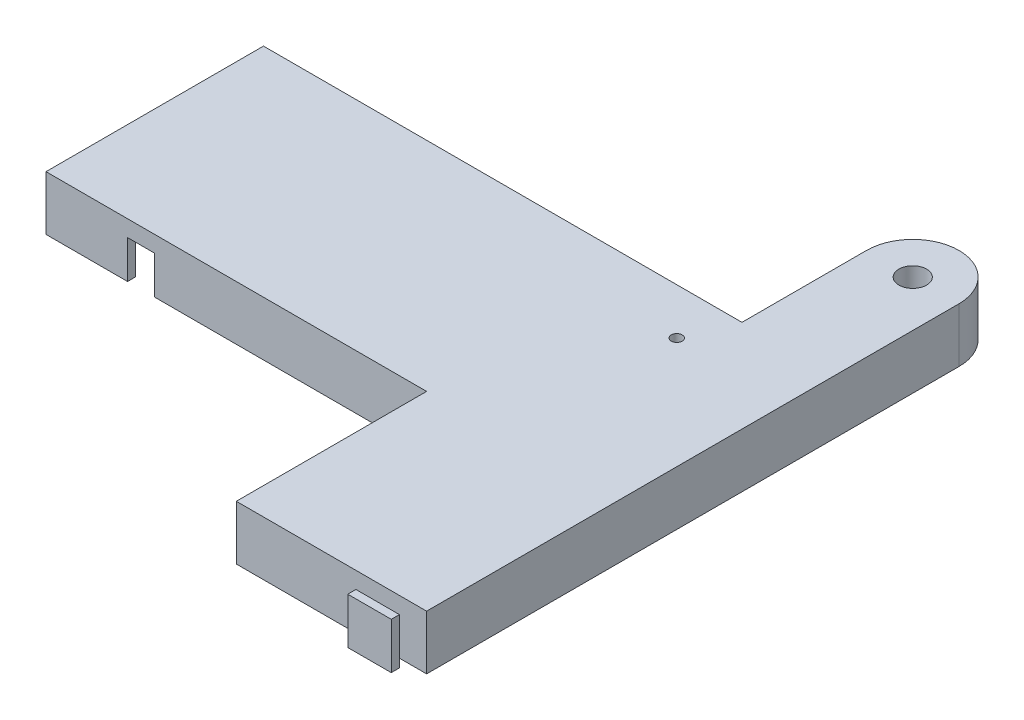
SolidWorks part; units mm, degrees
ref_plane "Front Plane" through (0, 0, 0) normal (0, 0, 1) x (1, 0, 0)
ref_plane "Top Plane" through (0, 0, 0) normal (0, 1, 0) x (1, 0, 0)
ref_plane "Right Plane" through (0, 0, 0) normal (1, 0, 0) x (0, 0, -1)
sketch "CornerSketch1" plane through (0, 0, 0) normal (0, 1, 0) x (1, 0, 0)
  line L0 (210, -70) -> (140, -70)
  line L2 (0, 80) -> (176, 80)
  line L5 (140, -70) -> (140, 0)
  line L6 (140, 0) -> (0, 0)
  line L7 (0, 80) -> (0, 0)
  line L8 (176, 125.825) -> (176, 80)
  line L10 (210, 125.825) -> (210, -70)
  arc A0 (210, 125.825) -> (176, 125.825) centre (193, 125.825) ccw
  dimension "D3" = 34
  dimension "D4" = 70
  dimension "D6" = 45.825
  dimension "D2" = 210
  dimension "D5" = 150
  dimension "D7" = 80
extrude "CornerBoss-Extrude1" add sketch "CornerSketch1" along normal blind 20
shell "Shell1" thickness 3 removed face at (131.5, 0, -36.0813)
sketch "PadSketch2" plane through (0, 17, 0) normal (0, -1, 0) x (1, 0, 0)
  line L0 (210, 70) -> (210, -125.825) construction
  line L1 (176, -80) -> (0, -80) construction
  circle A0 centre (193, -125.825) radius 12
  circle A1 centre (169, -63) radius 5
  dimension "D2" = 10
  dimension "D1" = 24
  dimension "D3" = 41
  dimension "D4" = 17
extrude "PadBoss-Extrude2" add sketch "PadSketch2" along normal blind 10
sketch "StepperRodHoleSketch3" plane through (0, 7, 0) normal (0, -1, 0) x (1, 0, 0)
  circle A0 centre (193, -125.825) radius 5.1
  circle A1 centre (169, -63) radius 2
  dimension "D1" = 10.2
  dimension "D2" = 4
extrude "StepperRodHoleCut-Extrude1" cut sketch "StepperRodHoleSketch3" against normal through all
sketch "ThreadedNutMountHolesSketch4" plane through (0, 7, 0) normal (0, -1, 0) x (-1, 0, 0)
  circle A8 centre (-193, 133.825) radius 1
  circle A9 centre (-185, 125.825) radius 1
  circle A10 centre (-201, 125.825) radius 1
  circle A11 centre (-193, 117.825) radius 1
  dimension "D1" = 2
  dimension "D3" = 16
  dimension "D4" = 8
  dimension "D5" = 16
extrude "ThreadedNutMountHolesCut-Extrude2" cut sketch "ThreadedNutMountHolesSketch4" against normal blind 10
sketch "TLPegHoleSketch1" plane through (0, 0, 0) normal (-1, 0, 0) x (0, 0, 1)
  line L1 (-70, 14) -> (-60, 14)
  line L2 (-70, 14) -> (-70, 0)
  line L3 (-70, 0) -> (-60, 0)
  line L4 (-60, 14) -> (-60, 0)
  line L7 (-80, 0) -> (0, 0) construction
  line L8 (-80, 20) -> (-80, 0) construction
  dimension "D2" = 10
  dimension "D1" = 10
  dimension "D3" = 14
extrude "TLPegHoleCut-Extrude1" cut sketch "TLPegHoleSketch1" against normal blind 3
sketch "BottomPegSketch2" plane through (0, 0, 70) normal (0, 0, 1) x (1, 0, 0)
  line L1 (190.1, 13.9) -> (199.9, 13.9)
  line L2 (190.1, 13.9) -> (190.1, 0)
  line L3 (190.1, 0) -> (199.9, 0)
  line L4 (199.9, 13.9) -> (199.9, 0)
  line L6 (210, 20) -> (210, 0) construction
  line L7 (140, 0) -> (210, 0) construction
  dimension "D2" = 13.9
  dimension "D3" = 9.8
  dimension "D1" = 10.1
extrude "BottomPegBoss-Extrude1" add sketch "BottomPegSketch2" along normal blind 3.1
sketch "BottomPegCapSketch3" plane through (0, 0, 73.1) normal (0, 0, 1) x (1, 0, 0)
  line L1 (187.1, 17) -> (203.1, 17)
  line L2 (187.1, 17) -> (187.1, 0)
  line L3 (187.1, 0) -> (203.1, 0)
  line L4 (203.1, 17) -> (203.1, 0)
  line L6 (140, 0) -> (190.1, 0) construction
  line L7 (190.1, 13.9) -> (190.1, 0) construction
  dimension "D1" = 16
  dimension "D3" = 17
  dimension "D2" = 3
extrude "BottomPegCapBoss-Extrude2" add sketch "BottomPegCapSketch3" along normal blind 3
sketch "BedCenterHoleCutSketch1" plane through (0, 0, 0) normal (0, 0, 1) x (1, 0, 0)
  line L0 (0, 0) -> (140, 0) construction
  line L1 (30, 14) -> (40, 14)
  line L2 (30, 14) -> (30, 0)
  line L3 (30, 0) -> (40, 0)
  line L4 (40, 14) -> (40, 0)
  line L5 (140, 20) -> (140, 0) construction
  dimension "D2" = 10
  dimension "D1" = 14
  dimension "D3" = 100
extrude "BedCenterHoleCut-Extrude1" cut sketch "BedCenterHoleCutSketch1" against normal blind 3
equation "\"BedThickness\"= 20mm"
equation "\"BedToBuildPlateStandoffHolesDistanceFromLeftOrRight\"= \"BuildPlateStandoffHolesDistanceFromLeftOrRight\" + \"BedIncreasedByWidth\" / 2'Equals 17"
equation "\"BedToBuildPlateStandoffHolesDistanceFromBack\"= \"BuildPlateStandoffHolesDistanceFromBack\" + \"BedIncreasedByLength\" / 2'Equals 41"
equation "\"BedLLongSide\"= \"BedThirdSize\" * 3'Equals 210"
equation "\"BedLShortSide\"= \"BedThirdSize\" * 2'Equals 140"
equation "\"BedIncreasedByWidth\"= 20mm"
equation "\"BedIncreasedByLength\"= 0mm"
equation "\"BedThirdSize\"= 70mm"
equation "\"BedOverlap\"= 20mm"
equation "\"D3@TLPegHoleSketch1\"=\"BedPegHoleHeight\""
equation "\"StandardWallThickness\"= 3mm"
equation "\"D1@CornerBoss-Extrude1\"=\"BedThickness\""
equation "\"D1@TLPegHoleCut-Extrude1\" = \"StandardWallThickness\""
equation "\"D1@BottomPegBoss-Extrude1\"=\"BedPegBoss\""
equation "\"D2@BottomPegCapSketch3\"=\"StandardWallThickness\""
equation "\"D1@BottomPegCapBoss-Extrude2\" = \"StandardWallThickness\""
equation "\"LeadScrewNutPadSize\"= \"LeadScrewNutMountingHoleFlangeDiameter\" + 2mm'Equals 24"
equation "\"BedToBuildPlateStandoffPadSize\"= 10mm"
equation "\"D1@PadSketch2\" = \"LeadScrewNutPadSize\""
equation "\"D2@PadSketch2\" = \"BedToBuildPlateStandoffPadSize\""
equation "\"D3@PadSketch2\"=\"BedToBuildPlateStandoffHolesDistanceFromBack\""
equation "\"D4@PadSketch2\"=\"BedToBuildPlateStandoffHolesDistanceFromLeftOrRight\""
equation "\"D2@StepperRodHoleSketch3\"=\"M3HeatInsertHoleDiameter\""
equation "\"BuildPlateStandoffHolesDistanceFromLeftOrRight\"= 7mm"
equation "\"BuildPlateStandoffHolesDistanceFromBack\"= 41mm"
equation "\"D1@StepperRodHoleSketch3\"=\"LeadScrewNutInnerShaftFlangeDiameter\""
equation "\"BedLWidth\"= \"BedThirdSize\"'Equals 70"
equation "\"D4@CornerSketch1\"=\"BedLWidth\" + \"BedIncreasedByLength\"/2"
equation "\"D2@CornerSketch1\"=\"BedLLongSide\""
equation "\"D7@CornerSketch1\"=\"BedLWidth\" +\"BedOverlap\"/2"
equation "\"DistanceFromBedSideToStepperHole\"= ( \"DistanceBetweenLeftToRightStepperHoles\" - \"BedWidth\" ) / 2'Equals 45.825"
equation "\"RailThickness\"= .125in'Spec"
equation "\"DistanceBetweenLeftToRightStepperHoles\"= \"FrontBackRailLength\" - \"StepperMountingHoleOffsetFromLeftOrRightSide\" * 2 - \"StepperMountingHoleDistance\"'Equals 461.65"
equation "\"BedInnerSquareWidth\"= \"BedThirdSize\" * 3'Equals 210"
equation "\"FrontBackRailLength\"= 510mm"
equation "\"StepperMountingHoleOffsetFromItsSide\"= 5.5mm'Spec"
equation "\"StepperMountingHoleOffsetFromLeftOrRightSide\"= \"StepperMountingHoleOffsetFromItsSide\" + \"RailThickness\""
equation "\"StepperMountingHoleDistance\"= 31mm'Spec"
equation "\"BedWidth\"= \"BedInnerSquareWidth\" + \"BedLWidth\" * 2 + \"BedIncreasedByWidth\"'Equals 370"
equation "\"D6@CornerSketch1\"=\"DistanceFromBedSideToStepperHole\""
equation "\"DistanceFromBedFrontToStepperHole\"= \"LeadScrewNutPadSize\" + 10mm"
equation "\"D3@CornerSketch1\"=\"DistanceFromBedFrontToStepperHole\""
equation "\"D5@CornerSketch1\"=\"BedLShortSide\" +\"BedIncreasedByWidth\"/2"
equation "\"LeadScrewNutInnerShaftFlangeDiameter\"= 10.2mm'Spec"
equation "\"LeadScrewNutMountHoleDiameter\"= 2mm'Spec is 4.1 but smaller for tapping"
equation "\"LeadScrewNutMountingHoleFlangeDiameter\"= 22mm'Spec"
equation "\"LeadScrewNutMountingHoleDistance\"= 16mm'Spec"
equation "\"D3@ThreadedNutMountHolesSketch4\"=\"LeadScrewNutMountingHoleDistance\""
equation "\"D4@ThreadedNutMountHolesSketch4\"=\"LeadScrewNutMountingHoleDistance\"/2"
equation "\"D5@ThreadedNutMountHolesSketch4\"=\"LeadScrewNutMountingHoleDistance\""
equation "\"D2@ThreadedNutMountHolesSketch4\"=\"LeadScrewNutMountingHoleDistance\"/2"
equation "\"D1@ThreadedNutMountHolesSketch4\"=\"LeadScrewNutMountHoleDiameter\""
equation "\"LeadScrewNutPadDepth\"= \"BedThickness\" / 2'Equals 10"
equation "\"D1@ThreadedNutMountHolesCut-Extrude2\"=\"LeadScrewNutPadDepth\""
equation "\"D1@PadBoss-Extrude2\"= \"LeadScrewNutPadDepth\""
equation "\"BedPegHoleWidth\"= 10mm"
equation "\"BedPegHoleHeight\"= \"BedThickness\" - \"StandardWallThickness\" * 2'Equals 14"
equation "\"BedPegWidth\"= \"BedPegHoleWidth\" - .1mm * 2'For easier assembly"
equation "\"BedPegHeight\"= \"BedPegHoleHeight\" - .1mm'For easier assembly"
equation "\"BedTopPegOffsetFromSide\"= 10mm"
equation "\"BedPegBoss\"= \"StandardWallThickness\" + .1mm'For easier assembly"
equation "\"BedPegCapHeight\"= \"BedThickness\" - \"StandardWallThickness\"'Equals 17"
equation "\"BedPegCapWidth\"= \"BedThickness\" / 2 + \"StandardWallThickness\" * 2'Equals 16"
equation "\"D1@TLPegHoleSketch1\"=\"BedTopPegOffsetFromSide\""
equation "\"D2@TLPegHoleSketch1\"=\"BedPegHoleWidth\""
equation "\"D3@BottomPegSketch2\"=\"BedPegWidth\""
equation "\"D2@BottomPegSketch2\"=\"BedPegHeight\""
equation "\"D1@BottomPegCapSketch3\"=\"BedPegCapWidth\""
equation "\"D3@BottomPegCapSketch3\"=\"BedPegCapHeight\""
equation "\"D1@BedCenterHoleCutSketch1\" = \"BedPegHoleHeight\""
equation "\"D2@BedCenterHoleCutSketch1\" = \"BedPegHoleWidth\""
equation "\"D3@BedCenterHoleCutSketch1\" = \"BedInnerSquareWidth\" / 2 - \"BedPegHoleWidth\" / 2"
equation "\"D1@BedCenterHoleCut-Extrude1\"=\"StandardWallThickness\""
equation "\"M3HeatInsertHoleDiameter\"= 4mm'Spec"
